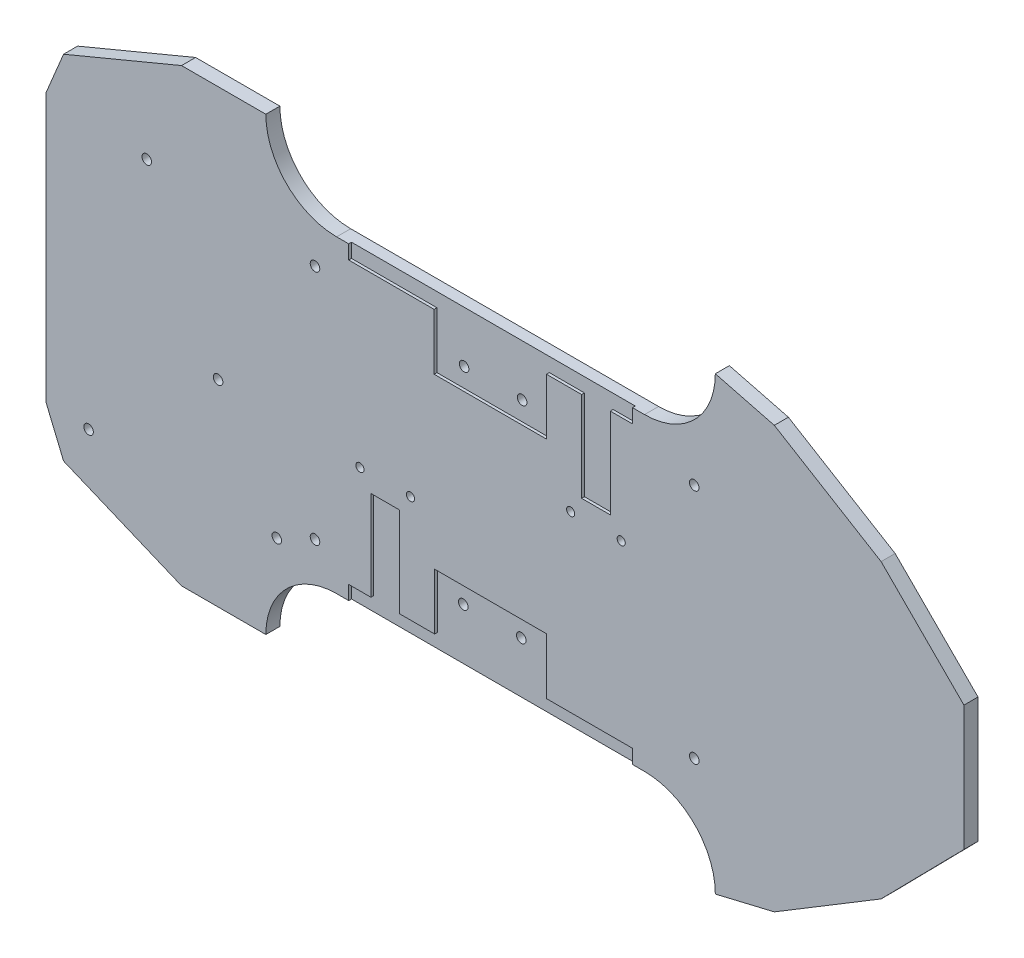
SolidWorks part; units mm, degrees
material "ABS PC"
ref_plane "Plan de face" through (0, 0, 0) normal (0, 0, 1) x (1, 0, 0)
ref_plane "Plan de dessus" through (0, 0, 0) normal (0, 1, 0) x (1, 0, 0)
ref_plane "Plan de droite" through (0, 0, 0) normal (1, 0, 0) x (0, 0, -1)
sketch "Esquisse1" plane through (0, 0, 0) normal (0, 0, 1) x (1, 0, 0)
  line L0 (-87.472, 59.5843) -> (-117.472, 59.5843)
  line L1 (-87.472, -100.8157) -> (-117.472, -100.8157)
  line L2 (-117.472, -100.8157) -> (-159.472, -83.3157)
  line L3 (-159.472, -83.3157) -> (-165.722, -68.3157)
  line L4 (72.528, -100.8157) -> (93.528, -95.8157)
  line L5 (-165.722, -68.3157) -> (-165.722, 27.0843)
  line L7 (-62.272, 34.3843) -> (47.328, 34.3843)
  line L8 (93.528, -95.8157) -> (131.528, -72.8157)
  line L9 (-165.722, 27.0843) -> (-159.472, 42.0843)
  line L10 (131.528, -72.8157) -> (161.028, -42.8157)
  line L11 (161.028, -42.8157) -> (161.028, 1.6843)
  line L12 (161.028, 1.6843) -> (131.528, 31.1843)
  line L13 (-62.272, -75.6157) -> (47.328, -75.6157)
  line L14 (131.528, 31.1843) -> (93.528, 54.1843)
  line L15 (93.528, 54.1843) -> (72.528, 59.5843)
  line L16 (-159.472, 42.0843) -> (-117.472, 59.5843)
  arc A4 (-87.472, 59.5843) -> (-62.272, 34.3843) centre (-62.272, 59.5843) ccw
  arc A5 (-87.472, -100.8157) -> (-62.272, -75.6157) centre (-62.272, -100.8157) cw
  arc A6 (72.528, -100.8157) -> (47.328, -75.6157) centre (47.328, -100.8157) ccw
  arc A7 (72.528, 59.5843) -> (47.328, 34.3843) centre (47.328, 59.5843) cw
  point P7 (72.528, 59.5843)
  point P33 (161.028, -42.8157)
  point P37 (161.028, 1.6843)
  point P39 (93.528, -95.8157)
  dimension "D16" = 102.5
  dimension "D17" = 59
  dimension "D18" = 72
  dimension "D19" = 17.5
  dimension "D9" = 25.2
  dimension "D28" = 25.2
  dimension "D25" = 25.2
  dimension "D30" = 25.2
  dimension "D8" = 59
  dimension "D22" = 132
  dimension "D12" = 30
  dimension "D20" = 72
  dimension "D33" = 109.6
  dimension "D4" = 25.2
  dimension "D5" = 25.2
  dimension "D6" = 5
  dimension "D7" = 21
  dimension "D10" = 160
  dimension "D11" = 28
  dimension "D13" = 58
  dimension "D14" = 88.5
  dimension "D15" = 30
  dimension "D21" = 160
  dimension "D23" = 109.6
  dimension "D24" = 17.5
  dimension "D26" = 155
  dimension "D27" = 25.2
  dimension "D29" = 15
  dimension "D31" = 25.2
  dimension "D32" = 15
  dimension "D34" = 21
  dimension "D37" = 110
extrude "Boss.-Extru.1" add sketch "Esquisse1" along normal blind 5
hole_wizard "Dégagement M2.51" positions "Esquisse5" profile "Esquisse4" hole size "M2.5" standard "ISO"
sketch "Esquisse5" plane through (0, 0, 0) normal (0, 0, -1) x (-1, 0, 0)
  circle A0 centre (-21.028, -8.6656) radius 1.025 construction
  point P0 (-21.028, -8.6656)
  point P1 (-39.028, -8.6656)
  point P4 (35.972, -32.5657)
  point P7 (53.972, -32.5657)
sketch "Esquisse4" plane through (21.028, -8.6656, 0) normal (1, 0, 0) x (0, 1, 0)
  line L0 (0, 0) -> (0, 5.8712)
  line L1 (0, 5.8712) -> (1.45, 5)
  line L2 (1.45, 5) -> (1.45, 0)
  line L5 (1.45, 0) -> (0, 0)
  line L10 (0, 5.8712) -> (-1.45, 5) construction
  line L11 (0, -6.35) -> (0, 107.95) construction
  dimension "Diamètre du perçage" = 2.9
  dimension "Profondeur du perçage" = 5
  dimension "Angle de pointe" = 118
hole_wizard "Dégagement M31" positions "Esquisse7" profile "Esquisse6" hole size "M3" standard "ISO"
sketch "Esquisse7" plane through (0, 0, 0) normal (0, 0, -1) x (-1, 0, 0)
  point P1 (17.8966, 16.1343)
  point P4 (-2.7526, 16.1343)
  point P19 (18.1966, -57.3657)
  point P22 (-2.4526, -57.3657)
sketch "Esquisse6" plane through (-17.8966, 16.1343, 0) normal (1, 0, 0) x (0, 1, 0)
  line L0 (0, 0) -> (0, 7.0215)
  line L1 (0, 7.0215) -> (1.7, 6)
  line L2 (1.7, 6) -> (1.7, 0)
  line L5 (1.7, 0) -> (0, 0)
  line L10 (0, 7.0215) -> (-1.7, 6) construction
  line L11 (0, -6.35) -> (0, 107.95) construction
  dimension "Diamètre du perçage" = 3.4
  dimension "Profondeur du perçage" = 6
  dimension "Angle de pointe" = 118
hole_wizard "Dégagement M32" positions "Esquisse9" profile "Esquisse8" hole size "M3" standard "ISO"
sketch "Esquisse9" plane through (0, 0, 0) normal (0, 0, -1) x (-1, 0, 0)
  point P1 (69.972, -62.7289)
  point P4 (69.972, 21.4976)
  point P7 (-65.028, -62.7289)
  point P10 (-65.028, 21.4976)
sketch "Esquisse8" plane through (-69.972, -62.7289, 0) normal (1, 0, 0) x (0, 1, 0)
  line L0 (0, 0) -> (0, 6.0215)
  line L1 (0, 6.0215) -> (1.7, 5)
  line L2 (1.7, 5) -> (1.7, 0)
  line L5 (1.7, 0) -> (0, 0)
  line L10 (0, 6.0215) -> (-1.7, 5) construction
  line L11 (0, -6.35) -> (0, 107.95) construction
  dimension "Diamètre du perçage" = 3.4
  dimension "Profondeur du perçage" = 5
  dimension "Angle de pointe" = 118
sketch "Esquisse10" plane through (0, 0, 5) normal (0, 0, 1) x (1, 0, 0)
  line L0 (43.028, 34.3843) -> (43.028, 29.3843)
  line L1 (43.028, 29.3843) -> (35.128, 29.3843)
  line L2 (35.128, 29.3843) -> (35.128, -2.6157)
  line L3 (35.128, -2.6157) -> (24.928, -2.6157)
  line L4 (24.928, -2.6157) -> (24.928, 29.3843)
  line L5 (24.928, 29.3843) -> (12.428, 29.3843)
  line L8 (12.428, 29.3843) -> (12.428, 9.3843)
  line L9 (12.428, 9.3843) -> (-27.572, 9.3843)
  line L10 (-27.572, 9.3843) -> (-27.572, 29.3843)
  line L11 (-76.472, 29.3843) -> (71.528, 29.3843) construction
  line L12 (-27.572, 29.3843) -> (-57.972, 29.3843)
  line L13 (-57.972, 29.3843) -> (-57.972, 34.3843)
  line L15 (-57.972, 34.3843) -> (-57.972, 29.3843) construction
  line L16 (-57.972, 34.3843) -> (43.028, 34.3843)
  line L17 (43.028, 34.3843) -> (42.9276, 34.4822)
  line L18 (43.028, -75.6157) -> (43.028, -70.6157)
  line L19 (43.028, -70.6157) -> (12.4203, -70.6157)
  line L20 (12.4203, -70.6157) -> (12.4203, -50.6157)
  line L21 (12.4203, -50.6157) -> (-27.372, -50.6157)
  line L22 (-27.372, -50.6157) -> (-27.372, -70.6157)
  line L23 (71.528, -70.6157) -> (-76.472, -70.6157) construction
  line L24 (-27.372, -70.6157) -> (-36.072, -70.6157)
  line L25 (-36.072, -70.6157) -> (-39.872, -70.6157)
  line L26 (-39.872, -70.6157) -> (-39.872, -38.6157)
  line L27 (-39.872, -38.6157) -> (-50.072, -38.6157)
  line L28 (-50.072, -38.6157) -> (-50.072, -70.6157)
  line L29 (-50.072, -70.6157) -> (-57.972, -70.6157)
  line L30 (-57.972, -70.6157) -> (-57.972, -75.6157)
  line L31 (-57.972, -75.6157) -> (43.028, -75.6157)
  line L32 (43.028, -75.6157) -> (43.028, -75.7928)
  dimension "D1" = 40
  dimension "D2" = 32
  dimension "D3" = 12.5
  dimension "D4" = 32
  dimension "D5" = 12.5
  dimension "D6" = 20
extrude "Enlèv. mat.-Extru.1" cut sketch "Esquisse10" against normal blind 1 contours L18 L19 L20 L21 L22 L24 L25 L26 L27 L28 L29 L30 L31
extrude "Enlèv. mat.-Extru.2" cut sketch "Esquisse10<3>" against normal blind 1 contours L13 L12 L10 L9 L8 L5 L4 L3 L2 L1 L0 region at (-0.0183, 22.0533, 5)
sketch "Esquisse10<3>" plane through (0, 0, 5) normal (0, 0, 1) x (1, 0, 0) same geometry as "Esquisse10"
hole_wizard "Dégagement M33" positions "Esquisse13" profile "Esquisse12" hole size "M3" standard "ISO"
sketch "Esquisse13" plane through (0, 0, 0) normal (0, 0, -1) x (-1, 0, 0)
  point P1 (104.4714, -30.7157)
  point P3 (129.8714, 24.4843)
sketch "Esquisse12" plane through (-104.4714, -30.7157, 0) normal (1, 0, 0) x (0, 1, 0)
  line L0 (0, 0) -> (0, 7.0215)
  line L1 (0, 7.0215) -> (1.7, 6)
  line L2 (1.7, 6) -> (1.7, 0)
  line L5 (1.7, 0) -> (0, 0)
  line L10 (0, 7.0215) -> (-1.7, 6) construction
  line L11 (0, -6.35) -> (0, 107.95) construction
  dimension "Diamètre du perçage" = 3.4
  dimension "Profondeur du perçage" = 6
  dimension "Angle de pointe" = 118
hole_wizard "Dégagement M34" positions "Esquisse16" profile "Esquisse15" hole size "M3" standard "ISO"
sketch "Esquisse16" plane through (0, 0, 0) normal (0, 0, -1) x (-1, 0, 0)
  point P8 (150.5714, -69.1157)
  point P10 (83.5714, -69.1157)
sketch "Esquisse15" plane through (-150.5714, -69.1157, 0) normal (1, 0, 0) x (0, 1, 0)
  line L0 (0, 0) -> (0, 6.0215)
  line L1 (0, 6.0215) -> (1.7, 5)
  line L2 (1.7, 5) -> (1.7, 0)
  line L5 (1.7, 0) -> (0, 0)
  line L10 (0, 6.0215) -> (-1.7, 5) construction
  line L11 (0, -6.35) -> (0, 107.95) construction
  dimension "Diamètre du perçage" = 3.4
  dimension "Profondeur du perçage" = 5
  dimension "Angle de pointe" = 118
sketch "Esquisse14" plane through (0, 0, 5) normal (0, 0, 1) x (1, 0, 0)
  line L0 (-166.4714, -20.6163) -> (141.528, -20.6163) construction
ref_plane "Plan1" through (0, -20.6163, 0) normal (0, -1, 0) x (1, 0, 0)
